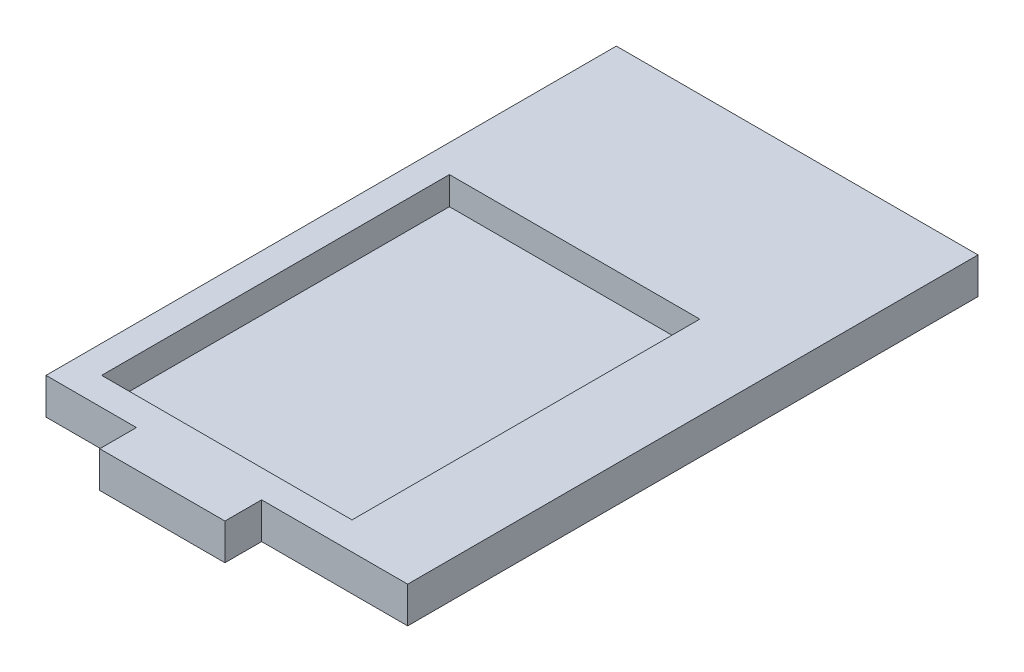
SolidWorks part; units mm, degrees
material "Natural Rubber"
ref_plane "Front Plane" through (0, 0, 0) normal (0, 0, 1) x (1, 0, 0)
ref_plane "Top Plane" through (0, 0, 0) normal (0, 1, 0) x (1, 0, 0)
ref_plane "Right Plane" through (0, 0, 0) normal (1, 0, 0) x (0, 0, -1)
sketch "Sketch1" plane through (0, 0, 0) normal (0, 1, 0) x (1, 0, 0)
  line L0 (45, 0) -> (45, -23.1837) construction
  line L1 (0, 0) -> (90, 0)
  line L2 (0, 0) -> (0, 125)
  line L3 (0, 125) -> (90, 125)
  line L4 (90, 0) -> (90, 125)
  line L5 (-10, -10) -> (120, -10)
  line L6 (-10, -10) -> (-10, 195)
  line L7 (-10, 195) -> (120, 195)
  line L8 (120, -10) -> (120, 195)
  line L9 (22.5, -10) -> (67.5, -10)
  line L10 (22.5, -10) -> (22.5, -23.1837)
  line L11 (22.5, -23.1837) -> (67.5, -23.1837)
  line L12 (67.5, -10) -> (67.5, -23.1837)
  point P16 (45, -23.1837)
  dimension "D1" = 90
  dimension "D2" = 125
  dimension "D3" = 10
  dimension "D4" = 10
  dimension "D5" = 30
  dimension "D6" = 70
  dimension "D7" = 45
extrude "Boss-Extrude1" add sketch "Sketch1" against normal blind 3 contours L1 L4 L3 L2 | L5 L8 L7 L6 L4 L1 L2 L3 | L2 L1 L4 L3 | L6 L5 L8 L7 | L10 L9 L12 L11 region at (45, 0, -62.5) region at (-7.5726, 0, -92.5)
extrude "Boss-Extrude2" add sketch "Sketch1<3>" along normal blind 10 contours L4 L1 L9 L5 L8 L7 L6 L2 L3 | L0 L5 L10 L11 | L9 L0 L11 L12 region at (33.75, 0, 7.5726) region at (56.25, 0, 16.5918) region at (33.75, 0, 16.5918)
sketch "Sketch1<3>" plane through (0, 0, 0) normal (0, 1, 0) x (1, 0, 0) same geometry as "Sketch1"
